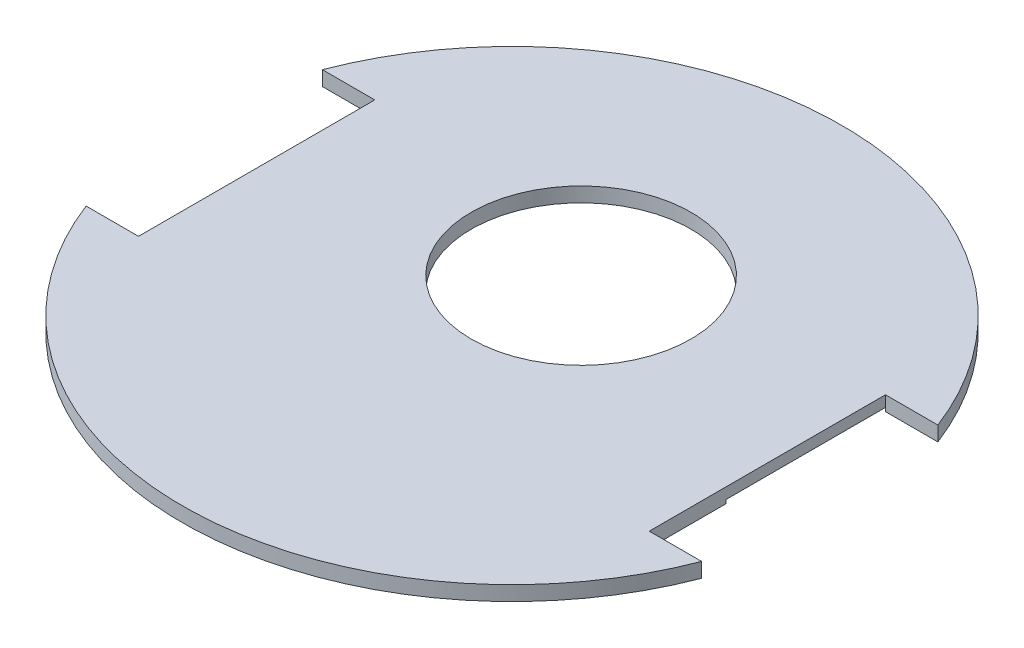
SolidWorks part; units mm, degrees
ref_plane "前基準面" through (0, 0, 0) normal (0, 0, 1) x (1, 0, 0)
ref_plane "上基準面" through (0, 0, 0) normal (0, 1, 0) x (1, 0, 0)
ref_plane "右基準面" through (0, 0, 0) normal (1, 0, 0) x (0, 0, -1)
sketch "草圖2" plane through (0, 0, 0) normal (0, 1, 0) x (1, 0, 0)
  line L0 (0, 0) -> (0, 90) construction
  line L1 (69.7177, 32.25) -> (84.0234, 32.25)
  line L3 (69.7177, -32.25) -> (84.0234, -32.25)
  line L5 (69.7177, 32.25) -> (88.4704, -16.5222) construction
  line L6 (69.7177, -32.25) -> (88.4704, 16.5222) construction
  line L7 (-69.7177, -32.25) -> (-84.0234, -32.25)
  line L9 (-69.7177, 32.25) -> (-84.0234, 32.25)
  line L11 (-90, 0) -> (90, 0) construction
  line L12 (-37.85, -15.9948) -> (37.85, -15.9948)
  line L13 (-37.85, -15.9948) -> (-37.85, -76.6948)
  line L14 (-37.85, -76.6948) -> (37.85, -76.6948)
  line L15 (37.85, -15.9948) -> (37.85, -76.6948)
  line L16 (-37.85, -15.9948) -> (37.85, -76.6948) construction
  line L17 (-37.85, -76.6948) -> (37.85, -15.9948) construction
  line L18 (-69.7177, 54.159) -> (-47.3177, 54.159)
  line L20 (-69.7177, -11.341) -> (-47.3177, -11.341)
  line L21 (-47.3177, 54.159) -> (-47.3177, -11.341)
  line L22 (-69.7177, 54.159) -> (-47.3177, -11.341) construction
  line L23 (-69.7177, -11.341) -> (-47.3177, 54.159) construction
  line L24 (69.7177, -11.341) -> (47.3177, -11.341)
  line L25 (47.3177, 54.159) -> (47.3177, -11.341)
  line L27 (69.7177, 54.159) -> (47.3177, 54.159)
  line L28 (69.7177, 54.159) -> (69.7177, -32.25)
  line L31 (-69.7177, 54.159) -> (-69.7177, -32.25)
  circle A0 centre (0, 0) radius 90
  circle A1 centre (0, 18.8688) radius 30
  circle A4 centre (0, 71.5758) radius 17.5
  point P5 (82.1177, 0)
  point P17 (0, -46.3448)
  point P23 (-58.5177, 21.409)
  dimension "D3" = 180
  dimension "D4" = 60
  dimension "D5" = 75.7
  dimension "D6" = 60.7
  dimension "D7" = 65.5
  dimension "D8" = 22.4
sketch "草圖3" plane through (0, 0, 0) normal (0, 0, 1) x (1, 0, 0)
  line L0 (0, 0) -> (0, 90) construction
  line L1 (69.7177, 32.25) -> (94.5177, 32.25)
  line L2 (69.7177, 32.25) -> (69.7177, -32.25)
  line L3 (69.7177, -32.25) -> (94.5177, -32.25)
  line L4 (94.5177, 32.25) -> (94.5177, -32.25)
  line L5 (69.7177, 32.25) -> (94.5177, -32.25) construction
  line L6 (69.7177, -32.25) -> (94.5177, 32.25) construction
  line L7 (-69.7177, -32.25) -> (-94.5177, -32.25)
  line L8 (-94.5177, 32.25) -> (-94.5177, -32.25)
  line L9 (-69.7177, 32.25) -> (-94.5177, 32.25)
  line L10 (-69.7177, 32.25) -> (-69.7177, -32.25)
  line L11 (-90, 0) -> (90, 0) construction
  line L17 (62.727, -15.2532) -> (18.727, -15.2532)
  line L22 (62.727, -15.2532) -> (62.727, -59.2532)
  line L23 (62.727, -59.2532) -> (18.727, -59.2532)
  line L28 (18.727, -15.2532) -> (18.727, -59.2532)
  line L29 (62.727, -15.2532) -> (18.727, -59.2532) construction
  line L30 (62.727, -59.2532) -> (18.727, -15.2532) construction
  line L31 (14.5242, -14.2532) -> (-63.8758, -14.2532)
  line L32 (14.5242, -14.2532) -> (14.5242, -60.2532)
  line L33 (14.5242, -60.2532) -> (-63.8758, -60.2532)
  line L34 (-63.8758, -14.2532) -> (-63.8758, -60.2532)
  line L35 (14.5242, -14.2532) -> (-63.8758, -60.2532) construction
  line L36 (14.5242, -60.2532) -> (-63.8758, -14.2532) construction
  circle A0 centre (0, 0) radius 90
  circle A1 centre (0, 18.8688) radius 30
  circle A4 centre (0, 71.5758) radius 17.5
  point P5 (82.1177, 0)
  point P17 (40.727, -37.2532)
  point P18 (-24.6758, -37.2532)
  point P23 (0, 21.409)
  dimension "D1" = 64.5
  dimension "D3" = 180
  dimension "D4" = 60
  dimension "D2" = 24.8
  dimension "D5" = 44
  dimension "D6" = 44
  dimension "D7" = 78.4
  dimension "D8" = 46
sketch "草圖4" plane through (0, 0, 0) normal (0, 0, 1) x (1, 0, 0)
  line L0 (0, 90) -> (0, -90) construction
  line L26 (61.98, 22.7) -> (75.98, 22.7)
  line L27 (61.98, 22.7) -> (61.98, -22.7)
  line L28 (61.98, -22.7) -> (75.98, -22.7)
  line L29 (75.98, 22.7) -> (75.98, -22.7)
  line L30 (61.98, 22.7) -> (75.98, -22.7) construction
  line L31 (61.98, -22.7) -> (75.98, 22.7) construction
  line L36 (-22.7, 76.435) -> (22.7, 76.435)
  line L37 (-22.7, 76.435) -> (-22.7, 62.435)
  line L38 (-22.7, 62.435) -> (22.7, 62.435)
  line L39 (22.7, 76.435) -> (22.7, 62.435)
  line L40 (-22.7, 76.435) -> (22.7, 62.435) construction
  line L41 (-22.7, 62.435) -> (22.7, 76.435) construction
  circle A0 centre (0, 0) radius 90
  point P3 (0, 69.435)
  point P4 (0, -42.8824)
  point P10 (0, 26.4198)
  point P18 (68.98, 0)
  dimension "D1" = 180
  dimension "D6" = 45.4
  dimension "D7" = 14
  dimension "D8" = 45.4
  dimension "D9" = 14
sketch "草圖5" plane through (0, 0, 0) normal (0, 0, 1) x (1, 0, 0)
  line L0 (-1.6499, 90) -> (-1.6499, -90) construction
  line L12 (-28.5999, -8.3824) -> (25.3001, -8.3824)
  line L15 (-28.5999, -8.3824) -> (-28.5999, -77.3824)
  line L16 (-28.5999, -77.3824) -> (25.3001, -77.3824)
  line L17 (25.3001, -8.3824) -> (25.3001, -77.3824)
  line L18 (-28.5999, -8.3824) -> (25.3001, -77.3824) construction
  line L19 (-28.5999, -77.3824) -> (25.3001, -8.3824) construction
  line L20 (-45.6999, 54.5198) -> (42.4001, 54.5198)
  line L21 (-45.6999, 54.5198) -> (-45.6999, -1.6802)
  line L22 (-45.6999, -1.6802) -> (42.4001, -1.6802)
  line L23 (42.4001, 54.5198) -> (42.4001, -1.6802)
  line L24 (-45.6999, 54.5198) -> (42.4001, -1.6802) construction
  line L25 (-45.6999, -1.6802) -> (42.4001, 54.5198) construction
  line L30 (-28.5499, 71.2937) -> (25.2501, 71.2937) construction
  line L31 (-28.5499, 80.0937) -> (25.2501, 80.0937)
  line L35 (-28.5499, 62.4937) -> (25.2501, 62.4937)
  line L40 (-37.3499, 71.2937) -> (34.0501, 71.2937) construction
  line L41 (-91.6499, 0) -> (88.3501, 0) construction
  circle A0 centre (-1.6499, 0) radius 90
  arc A1 (-28.5499, 80.0937) -> (-28.5499, 62.4937) centre (-28.5499, 71.2937) ccw
  arc A2 (25.2501, 62.4937) -> (25.2501, 80.0937) centre (25.2501, 71.2937) ccw
  circle A3 centre (-73.0763, 0) radius 10.5
  circle A4 centre (69.7766, 0) radius 10.5
  point P4 (-1.6499, -42.8824)
  point P10 (-1.6499, 26.4198)
  point P17 (-1.6499, 71.2937)
  dimension "D1" = 180
  dimension "D8" = 21
  dimension "D2" = 53.9
  dimension "D3" = 69
  dimension "D4" = 88.1
  dimension "D5" = 56.2
  dimension "D6" = 17.6
  dimension "D7" = 71.4
extrude "填料-伸長1" add sketch "草圖2" along normal blind 4 contours A0
extrude "除料-伸長1" cut sketch "草圖2<5>" against normal blind 10 and the other way through all contours L9 A0 L7 L31 | L3 A0 L1 L28 region at (78.9622, 0, 0) region at (-78.9622, 0, 0)
sketch "草圖2<5>" plane through (0, 0, 0) normal (0, 1, 0) x (1, 0, 0) same geometry as "草圖2"
extrude "除料-伸長2" cut sketch "草圖2<7>" against normal blind 1 and the other way blind 1 contours L18 L31 L20 L21 | L28 L27 L25 L24 region at (58.5177, 0, -21.409) region at (-58.5177, 0, -21.409)
sketch "草圖2<7>" plane through (0, 0, 0) normal (0, 1, 0) x (1, 0, 0) same geometry as "草圖2"
extrude "除料-伸長4" cut sketch "草圖2<8>" along normal through all contours A1
sketch "草圖2<8>" plane through (0, 0, 0) normal (0, 1, 0) x (1, 0, 0) same geometry as "草圖2"
extrude "除料-伸長5" cut sketch "草圖2<9>" against normal blind 1 and the other way blind 1 contours L15 L12 L13 L14 region at (0, 0, 46.3448)
sketch "草圖2<9>" plane through (0, 0, 0) normal (0, 1, 0) x (1, 0, 0) same geometry as "草圖2"
extrude "除料-伸長6" cut sketch "草圖2<10>" against normal blind 1 and the other way blind 1 contours A4
sketch "草圖2<10>" plane through (0, 0, 0) normal (0, 1, 0) x (1, 0, 0) same geometry as "草圖2"
